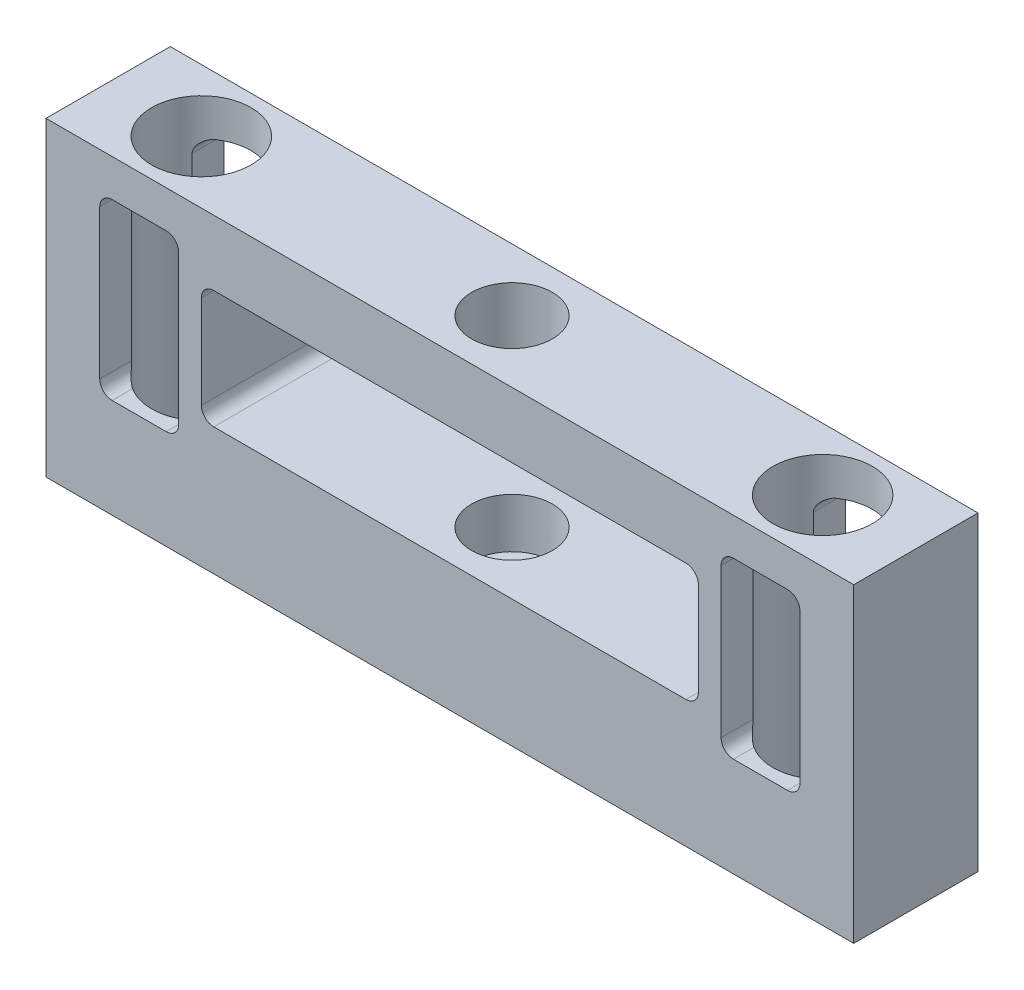
SolidWorks part; units mm, degrees
ref_plane "Front" through (0, 0, 0) normal (0, 0, 1) x (1, 0, 0)
ref_plane "Top" through (0, 0, 0) normal (0, 1, 0) x (1, 0, 0)
ref_plane "Right" through (0, 0, 0) normal (1, 0, 0) x (0, 0, -1)
sketch "Sketch1" plane through (0, 0, 0) normal (0, 0, 1) x (1, 0, 0)
  line L0 (0, 0) -> (0, 20) construction
  line L1 (38, 9.5) -> (-38, 9.5)
  line L2 (40, 7.5) -> (40, -7.5)
  line L3 (38, -9.5) -> (-38, -9.5)
  line L4 (-40, 7.5) -> (-40, -7.5)
  line L5 (40, 9.5) -> (-40, -9.5) construction
  line L6 (40, -9.5) -> (-40, 9.5) construction
  line L7 (65, 20) -> (-65, 20)
  line L8 (65, 20) -> (65, -30)
  line L9 (65, -30) -> (-65, -30)
  line L10 (-65, 20) -> (-65, -30)
  line L13 (0, 0) -> (-65, 0) construction
  line L14 (0, 0) -> (0, -30) construction
  arc A0 (40, 7.5) -> (38, 9.5) centre (38, 7.5) ccw
  arc A1 (38, -9.5) -> (40, -7.5) centre (38, -7.5) ccw
  arc A2 (-38, -9.5) -> (-40, -7.5) centre (-38, -7.5) cw
  arc A3 (-40, 7.5) -> (-38, 9.5) centre (-38, 7.5) cw
  point P0 (0, 0)
  point P18 (0, 0)
  dimension "D3" = 2
  dimension "D1" = 80
  dimension "D2" = 19
  dimension "D4" = 130
  dimension "D5" = 20
  dimension "D6" = 30
extrude "Boss-Extrude1" add sketch "Sketch1" along normal blind 10 and the other way blind 10
ref_plane "Plane1" through (0, 0, -5) normal (0, 0, 1) x (1, 0, 0)
sketch "Sketch2" plane through (0, 20, 0) normal (0, 1, 0) x (1, 0, 0)
  line L0 (-50, 10) -> (-50, -10) construction
  line L1 (65, 10) -> (-65, 10) construction
  line L2 (65, -10) -> (-65, -10) construction
  line L3 (-65, 0) -> (-50, 0) construction
  line L4 (-65, -10) -> (-65, 10) construction
  line L5 (0, 0) -> (0, -10) construction
  line L6 (65, 0) -> (50, 0) construction
  line L7 (50, 10) -> (50, -10) construction
  line L8 (-50, 0) -> (50, 0) construction
  circle A0 centre (-50, 0) radius 8
  circle A1 centre (50, 0) radius 8
  point P20 (0, 0)
  dimension "D1" = 15
extrude "Cut-Extrude1" cut sketch "Sketch2" against normal through all both and the other way through all
sketch "Sketch3" plane through (0, 0, -5) normal (0, 0, 1) x (1, 0, 0)
  line L0 (27, 0) -> (-27, 0)
  point P4 (0, 0)
  dimension "D1" = 54
ref_axis "Axis1" through (27, 0, -5) along (-1, 0, 0)
sketch "Sketch4" plane through (0, 0, -10) normal (0, 0, -1) x (-1, 0, 0)
  line L0 (0, 30) -> (0, -30) construction
  line L1 (65, -30) -> (-65, -30) construction
  line L2 (50, 0) -> (-50, 0) construction
  line L6 (43.65, -14) -> (56.35, 14) construction
  line L7 (-45.65, 14) -> (-54.35, 14)
  line L8 (-43.65, 12) -> (-43.65, -12)
  line L9 (-45.65, -14) -> (-54.35, -14)
  line L10 (-56.35, 12) -> (-56.35, -12)
  line L11 (-43.65, 14) -> (-56.35, -14) construction
  line L12 (-43.65, -14) -> (-56.35, 14) construction
  line L13 (43.65, 14) -> (56.35, -14) construction
  line L14 (56.35, 12) -> (56.35, -12)
  line L15 (45.65, -14) -> (54.35, -14)
  line L16 (43.65, 12) -> (43.65, -12)
  line L17 (45.65, 14) -> (54.35, 14)
  arc A0 (-54.35, -14) -> (-56.35, -12) centre (-54.35, -12) cw
  arc A1 (-45.65, -14) -> (-43.65, -12) centre (-45.65, -12) ccw
  arc A2 (-43.65, 12) -> (-45.65, 14) centre (-45.65, 12) ccw
  arc A3 (-56.35, 12) -> (-54.35, 14) centre (-54.35, 12) cw
  arc A4 (56.35, 12) -> (54.35, 14) centre (54.35, 12) ccw
  arc A5 (43.65, 12) -> (45.65, 14) centre (45.65, 12) cw
  arc A6 (45.65, -14) -> (43.65, -12) centre (45.65, -12) cw
  arc A7 (54.35, -14) -> (56.35, -12) centre (54.35, -12) ccw
  point P6 (0, 0)
  point P29 (0, 0)
  dimension "D4" = 2
  dimension "D1" = 50
  dimension "D2" = 28
  dimension "D3" = 12.7
extrude "Cut-Extrude2" cut sketch "Sketch4" against normal blind 23
sketch "Sketch5" plane through (0, 20, 0) normal (0, 1, 0) x (1, 0, 0)
  circle A0 centre (0, 0) radius 4
extrude "Cut-Extrude3" cut sketch "Sketch5" against normal through all both and the other way through all
sketch "Sketch6" plane through (0, 20, 0) normal (0, 1, 0) x (1, 0, 0)
  circle A0 centre (0, 0) radius 6.5
extrude "Cut-Extrude4" cut sketch "Sketch6" against normal blind 37.5
